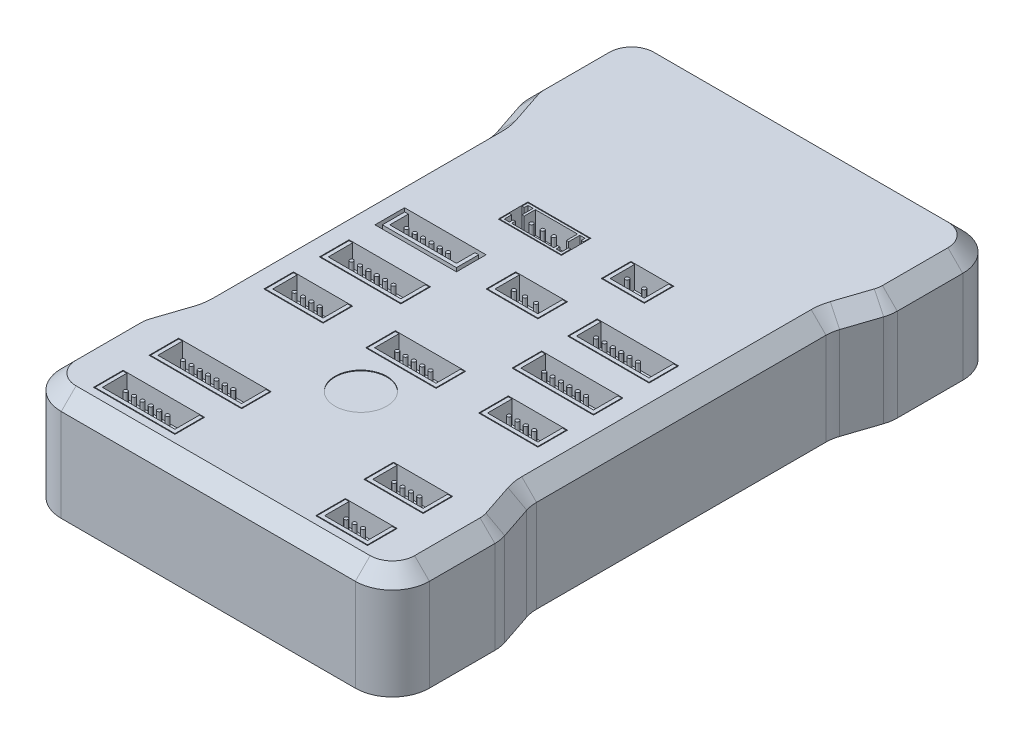
SolidWorks part; units mm, degrees
ref_plane "Front Plane" through (0, 0, 0) normal (0, 0, 1) x (1, 0, 0)
ref_plane "Top Plane" through (0, 0, 0) normal (0, 1, 0) x (1, 0, 0)
ref_plane "Right Plane" through (0, 0, 0) normal (1, 0, 0) x (0, 0, -1)
sketch "Sketch1" plane through (0, 0, 0) normal (0, 1, 0) x (1, 0, 0)
  line L6 (-19.85, 41) -> (19.85, 41)
  line L7 (24.85, 36) -> (24.85, 27.1614)
  line L8 (24.5934, 25.5802) -> (23.1066, 21.1198)
  line L9 (22.85, 19.5386) -> (22.85, -19.5386)
  line L12 (-22.85, 19.5386) -> (-22.85, -19.5386)
  line L13 (-24.5934, 25.5802) -> (-23.1066, 21.1198)
  line L14 (-24.85, 36) -> (-24.85, 27.1614)
  line L15 (-24.85, -36) -> (-24.85, -27.1614)
  line L16 (-24.5934, -25.5802) -> (-23.1066, -21.1198)
  line L17 (24.5934, -25.5802) -> (23.1066, -21.1198)
  line L18 (24.85, -36) -> (24.85, -27.1614)
  line L19 (-19.85, -41) -> (19.85, -41)
  arc A0 (19.85, 41) -> (24.85, 36) centre (19.85, 36) cw
  arc A1 (23.1066, 21.1198) -> (22.85, 19.5386) centre (27.85, 19.5386) ccw
  arc A2 (24.85, 27.1614) -> (24.5934, 25.5802) centre (19.85, 27.1614) cw
  arc A3 (-23.1066, 21.1198) -> (-22.85, 19.5386) centre (-27.85, 19.5386) cw
  arc A4 (-24.85, 27.1614) -> (-24.5934, 25.5802) centre (-19.85, 27.1614) ccw
  arc A5 (-19.85, 41) -> (-24.85, 36) centre (-19.85, 36) ccw
  arc A6 (-19.85, -41) -> (-24.85, -36) centre (-19.85, -36) cw
  arc A7 (-24.85, -27.1614) -> (-24.5934, -25.5802) centre (-19.85, -27.1614) cw
  arc A8 (-23.1066, -21.1198) -> (-22.85, -19.5386) centre (-27.85, -19.5386) ccw
  arc A9 (24.85, -27.1614) -> (24.5934, -25.5802) centre (19.85, -27.1614) ccw
  arc A10 (23.1066, -21.1198) -> (22.85, -19.5386) centre (27.85, -19.5386) cw
  arc A11 (19.85, -41) -> (24.85, -36) centre (19.85, -36) ccw
  point P8 (24.85, 41)
  point P12 (22.85, 20.35)
  point P15 (24.85, 26.35)
  point P44 (24.85, -26.35)
  point P45 (22.85, -20.35)
  point P46 (24.85, -41)
  point P48 (0, 0)
  dimension "D6" = 5
  dimension "D7" = 5
  dimension "D1" = 49.7
  dimension "D2" = 39.0772
  dimension "D3" = 82
  dimension "D4" = 2
  dimension "D5" = 6
  dimension "D8" = 41
extrude "Boss-Extrude1" add sketch "Sketch1" along normal blind 16
chamfer "Chamfer2" distance 2 angle 45 24 edges at (22.9146, 16, 20.3395) (22.85, 16, 0) (23.85, 16, 23.35) (22.9146, 16, -20.3395) (24.7854, 16, 26.3605) (23.85, 16, -23.35) (24.85, 16, 31.5807) (24.7854, 16, -26.3605) (23.3855, 16, 39.5355) (24.85, 16, -31.5807) (0, 16, 41) (23.3855, 16, -39.5355) (-23.3855, 16, 39.5355) (0, 16, -41) (-24.85, 16, 31.5807) (-23.3855, 16, -39.5355) (-24.7854, 16, 26.3605) (-24.85, 16, -31.5807) (-23.85, 16, 23.35) (-24.7854, 16, -26.3605) (-22.9146, 16, 20.3395) (-23.85, 16, -23.35) (-22.85, 16, 0) (-22.9146, 16, -20.3395)
chamfer "Chamfer3" distance 3.5 distance2 1.5 24 edges at (-22.85, 0, 0) (-22.9146, 0, 20.3395) (-22.9146, 0, -20.3395) (-23.85, 0, 23.35) (-23.85, 0, -23.35) (-24.7854, 0, 26.3605) (-24.7854, 0, -26.3605) (-24.85, 0, 31.5807) (-24.85, 0, -31.5807) (-23.3855, 0, 39.5355) (-23.3855, 0, -39.5355) (0, 0, 41) (0, 0, -41) (23.3855, 0, 39.5355) (23.3855, 0, -39.5355) (24.85, 0, 31.5807) (24.85, 0, -31.5807) (24.7854, 0, 26.3605) (24.7854, 0, -26.3605) (23.85, 0, 23.35) (23.85, 0, -23.35) (22.9146, 0, 20.3395) (22.9146, 0, -20.3395) (22.85, 0, 0) first distance on face at (0, 0, 0)
sketch "Sketch4" plane through (0, 0, 0) normal (0, -1, 0) x (1, 0, 0)
  line L0 (0, 0) -> (0, 37.5) construction
  line L1 (-18.35, 36.5) -> (-12.35, 36.5)
  line L2 (-20.35, 34.5) -> (-20.35, 28.5)
  line L3 (-18.35, 26.5) -> (-12.35, 26.5)
  line L4 (-10.35, 34.5) -> (-10.35, 28.5)
  line L5 (19.85, 37.5) -> (-19.85, 37.5) construction
  line L6 (0, 0) -> (-19.35, 0) construction
  line L7 (-19.35, 19.5386) -> (-19.35, -19.5386) construction
  line L8 (-21.35, 36) -> (-21.35, 27.1614) construction
  line L9 (18.35, 26.5) -> (12.35, 26.5)
  line L10 (10.35, 34.5) -> (10.35, 28.5)
  line L11 (18.35, 36.5) -> (12.35, 36.5)
  line L12 (20.35, 34.5) -> (20.35, 28.5)
  line L13 (20.35, -34.5) -> (20.35, -28.5)
  line L14 (18.35, -36.5) -> (12.35, -36.5)
  line L15 (10.35, -34.5) -> (10.35, -28.5)
  line L16 (18.35, -26.5) -> (12.35, -26.5)
  line L17 (-18.35, -26.5) -> (-12.35, -26.5)
  line L18 (-10.35, -34.5) -> (-10.35, -28.5)
  line L19 (-18.35, -36.5) -> (-12.35, -36.5)
  line L20 (-20.35, -34.5) -> (-20.35, -28.5)
  line L22 (-10.75, 17.75) -> (10.75, 17.75)
  line L23 (-12.75, 15.75) -> (-12.75, -15.75)
  line L24 (-10.75, -17.75) -> (10.75, -17.75)
  line L25 (12.75, 15.75) -> (12.75, -15.75)
  arc A0 (-12.35, 26.5) -> (-10.35, 28.5) centre (-12.35, 28.5) ccw
  arc A1 (-20.35, 28.5) -> (-18.35, 26.5) centre (-18.35, 28.5) ccw
  arc A2 (-18.35, 36.5) -> (-20.35, 34.5) centre (-18.35, 34.5) ccw
  arc A3 (-12.35, 36.5) -> (-10.35, 34.5) centre (-12.35, 34.5) cw
  arc A4 (12.35, 26.5) -> (10.35, 28.5) centre (12.35, 28.5) cw
  arc A5 (12.35, 36.5) -> (10.35, 34.5) centre (12.35, 34.5) ccw
  arc A6 (20.35, 28.5) -> (18.35, 26.5) centre (18.35, 28.5) cw
  arc A7 (18.35, 36.5) -> (20.35, 34.5) centre (18.35, 34.5) cw
  arc A8 (20.35, -28.5) -> (18.35, -26.5) centre (18.35, -28.5) ccw
  arc A9 (18.35, -36.5) -> (20.35, -34.5) centre (18.35, -34.5) ccw
  arc A10 (12.35, -36.5) -> (10.35, -34.5) centre (12.35, -34.5) cw
  arc A11 (12.35, -26.5) -> (10.35, -28.5) centre (12.35, -28.5) ccw
  arc A12 (-12.35, -26.5) -> (-10.35, -28.5) centre (-12.35, -28.5) cw
  arc A13 (-12.35, -36.5) -> (-10.35, -34.5) centre (-12.35, -34.5) ccw
  arc A14 (-20.35, -28.5) -> (-18.35, -26.5) centre (-18.35, -28.5) cw
  arc A15 (-18.35, -36.5) -> (-20.35, -34.5) centre (-18.35, -34.5) cw
  arc A16 (-12.75, -15.75) -> (-10.75, -17.75) centre (-10.75, -15.75) ccw
  arc A17 (10.75, -17.75) -> (12.75, -15.75) centre (10.75, -15.75) ccw
  arc A18 (10.75, 17.75) -> (12.75, 15.75) centre (10.75, 15.75) cw
  arc A19 (-10.75, 17.75) -> (-12.75, 15.75) centre (-10.75, 15.75) ccw
  point P16 (-10.35, 26.5)
  point P19 (-20.35, 26.5)
  point P24 (-10.35, 36.5)
  point P65 (0, -17.75)
  point P66 (-12.75, 0)
  point P69 (-12.75, -17.75)
  point P72 (12.75, -17.75)
  point P75 (12.75, 17.75)
  dimension "D5" = 2
  dimension "D8" = 2
  dimension "D1" = 10
  dimension "D2" = 10
  dimension "D3" = 1
  dimension "D4" = 1
  dimension "D6" = 35.5
  dimension "D7" = 25.5
extrude "Cut-Extrude2" cut sketch "Sketch4" against normal blind 0.5
sketch "Sketch5" plane through (0, 16, 0) normal (0, 1, 0) x (1, 0, 0)
  line L0 (-20.85, 19.5386) -> (-20.85, -19.5386) construction
  line L1 (-10.85, 13) -> (-2.35, 13)
  line L2 (-10.85, 13) -> (-10.85, 9)
  line L3 (-10.85, 9) -> (-2.35, 9)
  line L4 (-2.35, 13) -> (-2.35, 9)
  line L5 (3.05, 13) -> (8.85, 13)
  line L6 (3.05, 13) -> (3.05, 9)
  line L7 (3.05, 9) -> (8.85, 9)
  line L8 (8.85, 13) -> (8.85, 9)
  line L9 (20.85, -19.5386) -> (20.85, 19.5386) construction
  line L10 (19.85, 39) -> (-19.85, 39) construction
  line L11 (-18.5, -3.5) -> (-7.5, -3.5)
  line L12 (-18.5, 4) -> (-7.5, 4)
  line L13 (-18.5, 4) -> (-18.5, 0)
  line L14 (-18.5, 0) -> (-7.5, 0)
  line L15 (-7.5, 4) -> (-7.5, 0)
  line L16 (-3.5, 4) -> (3.5, 4)
  line L17 (-3.5, 4) -> (-3.5, 0)
  line L18 (-3.5, 0) -> (3.5, 0)
  line L19 (3.5, 4) -> (3.5, 0)
  line L20 (7.5, 4) -> (18.5, 4)
  line L21 (7.5, 4) -> (7.5, 0)
  line L22 (7.5, 0) -> (18.5, 0)
  line L23 (18.5, 4) -> (18.5, 0)
  line L24 (-18.5, -3.5) -> (-18.5, -7.5)
  line L25 (-18.5, -7.5) -> (-7.5, -7.5)
  line L26 (-7.5, -3.5) -> (-7.5, -7.5)
  line L27 (7.5, -3.5) -> (18.5, -3.5)
  line L28 (7.5, -3.5) -> (7.5, -7.5)
  line L29 (7.5, -7.5) -> (18.5, -7.5)
  line L30 (18.5, -3.5) -> (18.5, -7.5)
  line L31 (-19.85, -39) -> (19.85, -39) construction
  line L32 (-18.5, -11) -> (-10.5, -11)
  line L33 (-18.5, -11) -> (-18.5, -15)
  line L34 (-18.5, -15) -> (-10.5, -15)
  line L35 (-10.5, -11) -> (-10.5, -15)
  line L36 (-4.75, -11) -> (4.75, -11)
  line L37 (-4.75, -11) -> (-4.75, -15)
  line L38 (-4.75, -15) -> (4.75, -15)
  line L39 (4.75, -11) -> (4.75, -15)
  line L40 (10.5, -11) -> (18.5, -11)
  line L41 (10.5, -11) -> (10.5, -15)
  line L42 (10.5, -15) -> (18.5, -15)
  line L43 (18.5, -11) -> (18.5, -15)
  line L44 (-18.5, -34) -> (-7.5, -34)
  line L45 (-18.5, -34) -> (-18.5, -38)
  line L46 (-18.5, -38) -> (-7.5, -38)
  line L47 (-7.5, -34) -> (-7.5, -38)
  line L49 (-18.5, -26.5) -> (-6, -26.5)
  line L50 (-18.5, -26.5) -> (-18.5, -30.5)
  line L51 (-18.5, -30.5) -> (-6, -30.5)
  line L52 (-6, -26.5) -> (-6, -30.5)
  line L53 (18.5, -26.5) -> (10.5, -26.5)
  line L54 (18.5, -26.5) -> (18.5, -30.5)
  line L55 (18.5, -30.5) -> (10.5, -30.5)
  line L56 (10.5, -26.5) -> (10.5, -30.5)
  line L57 (18.5, -34) -> (11.5, -34)
  line L58 (18.5, -34) -> (18.5, -38)
  line L59 (18.5, -38) -> (11.5, -38)
  line L60 (11.5, -34) -> (11.5, -38)
  point P12 (3.05, 11)
  point P13 (-2.35, 11)
  point P49 (0, 4)
  point P51 (0, -11)
  dimension "D1" = 8.5
  dimension "D2" = 4
  dimension "D3" = 4
  dimension "D4" = 5.8
  dimension "D5" = 10
  dimension "D6" = 12
  dimension "D7" = 26
  dimension "D8" = 11
  dimension "D9" = 4
  dimension "D10" = 4
  dimension "D11" = 4
  dimension "D12" = 7
  dimension "D13" = 4
  dimension "D14" = 4
  dimension "D15" = 11
  dimension "D16" = 5
  dimension "D17" = 8
  dimension "D18" = 11
  dimension "D19" = 4
  dimension "D20" = 4
  dimension "D21" = 11
  dimension "D22" = 3.5
  dimension "D23" = 3.5
  dimension "D24" = 8
  dimension "D25" = 4
  dimension "D26" = 3.5
  dimension "D27" = 9.5
  dimension "D28" = 4
  dimension "D29" = 4
  dimension "D30" = 11
  dimension "D31" = 4
  dimension "D32" = 1
  dimension "D33" = 12.5
  dimension "D34" = 4
  dimension "D35" = 3.5
  dimension "D36" = 8
  dimension "D37" = 4
  dimension "D38" = 7
  dimension "D39" = 4
  dimension "D40" = 1
  dimension "D41" = 3.5
extrude "Cut-Extrude3" cut sketch "Sketch5" against normal blind 4
sketch "Sketch6" plane through (0, 12, 0) normal (0, 1, 0) x (1, 0, 0)
  line L0 (-10.85, 11) -> (-3.85, 11) construction
  line L1 (-10.85, 13) -> (-10.85, 9) construction
  line L2 (-2.35, 9) -> (-2.35, 13) construction
  line L25 (-9.85, 11) -> (-9.35, 11)
  line L27 (-6.6, 11) -> (-6.6, 9.5) construction
  line L46 (-9.45, 12.6) -> (-3.75, 12.6)
  line L47 (-3.75, 11.1) -> (-3.75, 12.6)
  line L48 (-3.45, 11.1) -> (-3.75, 11.1)
  line L49 (-3.45, 12.6) -> (-3.45, 11.1)
  line L50 (-2.75, 12.6) -> (-3.45, 12.6)
  line L51 (-2.75, 12.1) -> (-2.75, 12.6)
  line L52 (-2.45, 12.1) -> (-2.75, 12.1)
  line L53 (-2.45, 12.9) -> (-2.45, 12.1)
  line L54 (-10.75, 12.9) -> (-2.45, 12.9)
  line L55 (-10.75, 12.1) -> (-10.75, 12.9)
  line L56 (-10.75, 12.1) -> (-10.45, 12.1)
  line L57 (-10.45, 12.1) -> (-10.45, 12.6)
  line L58 (-10.45, 12.6) -> (-9.75, 12.6)
  line L59 (-9.75, 12.6) -> (-9.75, 11.1)
  line L60 (-9.75, 11.1) -> (-9.45, 11.1)
  line L61 (-9.45, 11.1) -> (-9.45, 12.6)
  line L62 (-2.75, 9.4) -> (-2.75, 10.4)
  line L63 (-2.75, 10.4) -> (-2.45, 10.4)
  line L64 (-2.45, 10.4) -> (-2.45, 9.1)
  line L65 (-10.75, 9.1) -> (-2.45, 9.1)
  line L66 (-10.75, 10.4) -> (-10.75, 9.1)
  line L67 (-10.45, 10.4) -> (-10.75, 10.4)
  line L68 (-10.45, 9.4) -> (-10.45, 10.4)
  line L69 (-9.75, 9.4) -> (-10.45, 9.4)
  line L70 (-9.75, 9.9) -> (-9.75, 9.4)
  line L71 (-9.45, 9.9) -> (-9.75, 9.9)
  line L72 (-9.45, 9.4) -> (-9.45, 9.9)
  line L73 (-3.75, 9.4) -> (-9.45, 9.4)
  line L74 (-3.75, 9.4) -> (-3.75, 9.9)
  line L75 (-3.75, 9.9) -> (-3.45, 9.9)
  line L76 (-3.45, 9.9) -> (-3.45, 9.4)
  line L77 (-3.45, 9.4) -> (-2.75, 9.4)
  line L78 (-10.85, 12) -> (-10.85, 13) construction
  line L79 (-10.85, 13) -> (-2.35, 13) construction
  line L80 (-10.85, 12) -> (-10.35, 12) construction
  line L81 (-10.35, 12) -> (-10.35, 12.5) construction
  line L82 (-10.35, 12.5) -> (-9.85, 12.5) construction
  line L83 (-9.85, 12.5) -> (-9.85, 11) construction
  line L84 (-2.35, 13) -> (-2.35, 12) construction
  line L85 (-2.35, 12) -> (-2.85, 12) construction
  line L86 (-2.85, 12) -> (-2.85, 12.5) construction
  line L87 (-2.85, 12.5) -> (-3.35, 12.5) construction
  line L88 (-3.35, 12.5) -> (-3.35, 11) construction
  line L89 (-3.35, 11) -> (-2.35, 11) construction
  line L90 (-3.35, 11) -> (-3.85, 11) construction
  line L91 (-3.85, 11) -> (-3.85, 12.5) construction
  line L92 (-9.35, 12.5) -> (-3.85, 12.5) construction
  line L93 (-9.35, 11) -> (-9.35, 12.5) construction
  dimension "D2" = 0.5
  dimension "D8" = 0.1
extrude "Boss-Extrude2" add sketch "Sketch6" along normal up to surface (4 mm away) contours L60 L61 L46 L47 L48 L49 L50 L51 L52 L53 L54 L55 L56 L57 L58 L59 | L77 L76 L75 L74 L73 L72 L71 L70 L69 L68 L67 L66 L65 L64 L63 L62 region at (-9.5349, 12, -11.85) region at (-2.666, 12, -9.9) up to face at (13, 16, -2)
sketch "Sketch7" plane through (0, 12, 0) normal (0, 1, 0) x (1, 0, 0)
  line L0 (-10.75, 9.1) -> (-2.45, 9.1) construction
  line L1 (-10.75, 12.9) -> (-2.45, 12.9) construction
  line L2 (-10.75, 9.1) -> (-2.45, 9.1)
  line L3 (-10.75, 12.9) -> (-2.45, 12.9)
  line L4 (-10.75, 12.9) -> (-10.75, 9.1)
  line L5 (-2.45, 12.9) -> (-2.45, 9.1)
extrude "Boss-Extrude3" add sketch "Sketch7" along normal blind 1
sketch "Sketch8" plane through (0, 13, 0) normal (0, 1, 0) x (1, 0, 0)
  line L6 (-10.75, 11) -> (-2.45, 11) construction
  circle A0 centre (-6.6, 10.75) radius 0.25
  circle A1 centre (-5.1, 10.75) radius 0.25
  circle A2 centre (-8.1, 10.75) radius 0.25
  point P9 (-6.6, 11)
  dimension "D1" = 0.5
  dimension "D2" = 0.25
  dimension "D3" = 1.5
  dimension "D4" = 1.5
extrude "Boss-Extrude4" add sketch "Sketch8" along normal up to surface (3 mm away) up to face at (13, 16, -2)
sketch "Sketch9" plane through (0, 12, 0) normal (0, 1, 0) x (1, 0, 0)
  line L0 (8.75, 12.9) -> (8.25, 12.9)
  line L1 (3.15, 12.9) -> (3.15, 9.1)
  line L2 (3.15, 9.1) -> (8.75, 9.1)
  line L3 (8.75, 9.1) -> (8.75, 12.9)
  line L4 (3.65, 12.9) -> (3.65, 9.6)
  line L5 (3.65, 9.6) -> (8.25, 9.6)
  line L6 (8.25, 9.6) -> (8.25, 12.9)
  line L7 (3.65, 12.9) -> (3.15, 12.9)
  line L8 (3.05, 13) -> (3.05, 9) construction
  line L9 (3.05, 9) -> (8.85, 9) construction
  line L10 (8.85, 9) -> (8.85, 13) construction
  line L11 (8.85, 13) -> (3.05, 13) construction
  dimension "D1" = 0.5
  dimension "D2" = 0.1
  dimension "D3" = 0.1
  dimension "D4" = 0.5
  dimension "D5" = 0.1
  dimension "D6" = 0.5
  dimension "D7" = 0.1
extrude "Boss-Extrude5" add sketch "Sketch9" along normal up to surface (4 mm away) up to face at (13, 16, -2)
sketch "Sketch10" plane through (0, 12, 0) normal (0, 1, 0) x (1, 0, 0)
  line L0 (8.75, 12.9) -> (8.75, 9.1) construction
  line L1 (3.15, 9.1) -> (8.75, 9.1) construction
  line L2 (3.15, 9.1) -> (3.15, 12.9) construction
  line L3 (3.15, 12.9) -> (3.65, 12.9) construction
  line L4 (8.75, 12.9) -> (8.75, 9.1)
  line L5 (3.15, 9.1) -> (8.75, 9.1)
  line L6 (3.15, 9.1) -> (3.15, 12.9)
  line L7 (3.15, 12.9) -> (3.65, 12.9)
  line L8 (3.65, 12.9) -> (8.75, 12.9)
extrude "Boss-Extrude6" add sketch "Sketch10" along normal blind 1
sketch "Sketch11" plane through (0, 13, 0) normal (0, 1, 0) x (1, 0, 0)
  line L0 (3.15, 11) -> (8.75, 11) construction
  line L1 (3.15, 12.9) -> (3.15, 9.1) construction
  line L2 (8.75, 9.1) -> (8.75, 12.9) construction
  circle A0 centre (4.8, 10.75) radius 0.25
  circle A1 centre (7.1, 10.75) radius 0.25
  point P10 (5.95, 11)
  dimension "D1" = 0.5
  dimension "D2" = 1.15
  dimension "D3" = 1.15
extrude "Boss-Extrude7" add sketch "Sketch11" along normal up to surface (3 mm away) up to face at (13, 16, -2)
sketch "Sketch12" plane through (0, 12, 0) normal (0, 1, 0) x (1, 0, 0)
  line L0 (-8, 3.5) -> (-18, 3.5)
  line L1 (-18, 3.5) -> (-18, 0.5)
  line L2 (-18, 0.5) -> (-8, 0.5)
  line L3 (-8, 0.5) -> (-8, 3.5)
extrude "Boss-Extrude8" add sketch "Sketch12" along normal blind 1
sketch "Sketch13" plane through (0, 13, 0) normal (0, 1, 0) x (1, 0, 0)
  line L0 (-18, 3.5) -> (-18, 0.5)
  line L1 (-18, 0.5) -> (-8, 0.5)
  line L2 (-8, 0.5) -> (-8, 3.5)
  line L3 (-8, 3.5) -> (-8.5, 3.5)
  line L4 (-8, 3.5) -> (-18, 3.5) construction
  line L5 (-8.5, 3.5) -> (-8.5, 1)
  line L6 (-8.5, 1) -> (-17.5, 1)
  line L7 (-17.5, 1) -> (-17.5, 3.5)
  line L8 (-17.5, 3.5) -> (-18, 3.5)
  dimension "D1" = 0.5
  dimension "D2" = 0.5
  dimension "D3" = 0.5
extrude "Boss-Extrude9" add sketch "Sketch13" along normal up to surface (3 mm away) up to face at (13, 16, -2)
sketch "Sketch14" plane through (0, 13, 0) normal (0, 1, 0) x (1, 0, 0)
  line L0 (-17.5, 2) -> (-8.5, 2) construction
  line L1 (-17.5, 1) -> (-17.5, 3.5) construction
  line L3 (-17.5, 3.5) -> (-17.5, 1) construction
  line L4 (-8.5, 1) -> (-8.5, 3.5) construction
  circle A0 centre (-16, 1.75) radius 0.25
  circle A1 centre (-14.875, 1.75) radius 0.25
  circle A2 centre (-13.75, 1.75) radius 0.25
  circle A3 centre (-12.625, 1.75) radius 0.25
  circle A5 centre (-11.5, 1.75) radius 0.25
  circle A6 centre (-10.375, 1.75) radius 0.25
  dimension "D1" = 0.5
  dimension "D2" = 1.5
  dimension "D3" = 1.125
  dimension "D4" = 1.125
  dimension "D5" = 1.125
  dimension "D6" = 1.125
  dimension "D7" = 1.125
extrude "Boss-Extrude10" add sketch "Sketch14" along normal up to surface (3 mm away) up to face at (13, 16, -2)
sketch "Sketch15" plane through (0, 12, 0) normal (0, 1, 0) x (1, 0, 0)
  line L0 (3.4, 3.9) -> (-3.4, 3.9)
  line L1 (-3.4, 3.9) -> (-3.4, 0.1)
  line L2 (-3.4, 0.1) -> (3.4, 0.1)
  line L3 (3.4, 0.1) -> (3.4, 3.9)
extrude "Boss-Extrude11" add sketch "Sketch15" along normal blind 1
sketch "Sketch16" plane through (0, 13, 0) normal (0, 1, 0) x (1, 0, 0)
  line L0 (-3.4, 0.1) -> (-3.4, 3.9)
  line L1 (-3.4, 3.9) -> (-2.9, 3.9)
  line L2 (3.4, 3.9) -> (-3.4, 3.9) construction
  line L3 (-2.9, 3.9) -> (-2.9, 0.6)
  line L4 (-2.9, 0.6) -> (2.9, 0.6)
  line L5 (2.9, 0.6) -> (2.9, 3.9)
  line L6 (2.9, 3.9) -> (3.4, 3.9)
  line L7 (3.4, 0.1) -> (3.4, 3.9) construction
  line L8 (3.4, 3.9) -> (3.4, 0.1)
  line L9 (3.4, 0.1) -> (-3.4, 0.1)
  point P15 (3.4, 2)
  dimension "D1" = 0.5
  dimension "D2" = 0.5
  dimension "D3" = 0.5
extrude "Boss-Extrude12" add sketch "Sketch16" along normal up to surface (3 mm away) up to face at (13, 16, -2)
sketch "Sketch17" plane through (0, 13, 0) normal (0, 1, 0) x (1, 0, 0)
  line L0 (-2.9, 2) -> (2.9, 2) construction
  line L1 (-2.9, 3.9) -> (-2.9, 0.6) construction
  line L2 (2.9, 3.9) -> (2.9, 0.6) construction
  circle A0 centre (0, 1.75) radius 0.25
  circle A1 centre (-1.5, 1.75) radius 0.25
  circle A2 centre (1.5, 1.75) radius 0.25
  point P14 (0, 1.5109)
  dimension "D1" = 0.5
  dimension "D2" = 0.5
  dimension "D3" = 1.5
  dimension "D4" = 1.5
extrude "Boss-Extrude13" add sketch "Sketch17" along normal up to surface (3 mm away) up to face at (13, 16, -2)
sketch "Sketch18" plane through (0, 12, 0) normal (0, 1, 0) x (1, 0, 0)
  line L0 (18.4, 3.9) -> (7.6, 3.9)
  line L1 (7.6, 3.9) -> (7.6, 0.1)
  line L2 (7.6, 0.1) -> (18.4, 0.1)
  line L3 (18.4, 0.1) -> (18.4, 3.9)
extrude "Boss-Extrude14" add sketch "Sketch18" along normal blind 1
sketch "Sketch19" plane through (0, 13, 0) normal (0, 1, 0) x (1, 0, 0)
  line L0 (7.6, 0.1) -> (7.6, 3.9)
  line L1 (7.6, 3.9) -> (8.1, 3.9)
  line L2 (18.4, 3.9) -> (7.6, 3.9) construction
  line L3 (8.1, 3.9) -> (8.1, 0.6)
  line L4 (8.1, 0.6) -> (17.9, 0.6)
  line L5 (17.9, 0.6) -> (17.9, 3.9)
  line L6 (17.9, 3.9) -> (18.4, 3.9)
  line L7 (18.4, 3.9) -> (7.6, 3.9) construction
  line L8 (18.4, 3.9) -> (18.4, 0.1)
  line L9 (18.4, 0.1) -> (7.6, 0.1)
  dimension "D1" = 0.5
  dimension "D2" = 0.5
  dimension "D3" = 0.5
extrude "Boss-Extrude15" add sketch "Sketch19" along normal up to surface (3 mm away) up to face at (13, 16, -2)
sketch "Sketch20" plane through (0, 13, 0) normal (0, 1, 0) x (1, 0, 0)
  line L0 (8.1, 1.997) -> (17.9, 1.997) construction
  line L1 (8.1, 3.9) -> (8.1, 0.6) construction
  line L2 (17.9, 3.9) -> (17.9, 0.6) construction
  line L3 (8.1, 0.6) -> (8.1, 3.9) construction
  circle A0 centre (14.1223, 1.747) radius 0.25
  circle A1 centre (15.2523, 1.747) radius 0.25
  circle A2 centre (11.8623, 1.75) radius 0.247
  circle A3 centre (10.7323, 1.747) radius 0.25
  circle A4 centre (12.9923, 1.75) radius 0.247
  circle A5 centre (9.6, 1.747) radius 0.25
  dimension "D1" = 0.5
  dimension "D2" = 0.5
  dimension "D3" = 1.1323
  dimension "D4" = 1.13
  dimension "D5" = 1.13
  dimension "D6" = 1.13
  dimension "D7" = 1.13
  dimension "D8" = 1.5
extrude "Boss-Extrude16" add sketch "Sketch20" along normal up to surface (3 mm away) up to face at (13, 16, -2)
sketch "Sketch22" plane through (0, 12, 0) normal (0, 1, 0) x (1, 0, 0)
  line L0 (-7.6, -3.6) -> (-18.4, -3.6)
  line L1 (-18.4, -3.6) -> (-18.4, -7.4)
  line L2 (-18.4, -7.4) -> (-7.6, -7.4)
  line L3 (-7.6, -7.4) -> (-7.6, -3.6)
extrude "Boss-Extrude17" add sketch "Sketch22" along normal blind 1
sketch "Sketch23" plane through (0, 13, 0) normal (0, 1, 0) x (1, 0, 0)
  line L0 (-18.4, -7.4) -> (-18.4, -3.6)
  line L1 (-18.4, -3.6) -> (-18.4, -7.4) construction
  line L2 (-18.4, -3.6) -> (-18.4, -7.4) construction
  line L3 (-18.4, -3.6) -> (-17.9, -3.6)
  line L4 (-7.6, -3.6) -> (-18.4, -3.6) construction
  line L5 (-17.9, -3.6) -> (-17.9, -6.9)
  line L6 (-17.9, -6.9) -> (-8.1, -6.9)
  line L7 (-8.1, -6.9) -> (-8.1, -3.6)
  line L8 (-8.1, -3.6) -> (-7.6, -3.6)
  line L9 (-7.6, -3.6) -> (-18.4, -3.6) construction
  line L10 (-7.6, -3.6) -> (-7.6, -7.4)
  line L11 (-7.6, -7.4) -> (-18.4, -7.4)
  dimension "D1" = 0.5
  dimension "D2" = 0.5
  dimension "D3" = 0.5
extrude "Boss-Extrude18" add sketch "Sketch23" along normal up to surface (3 mm away) up to face at (13, 16, -2)
sketch "Sketch24" plane through (0, 13, 0) normal (0, 1, 0) x (1, 0, 0)
  line L0 (-17.9, -5.5) -> (-8.1, -5.5) construction
  line L1 (-17.9, -3.6) -> (-17.9, -6.9) construction
  line L2 (-8.1, -3.6) -> (-8.1, -6.9) construction
  line L3 (-17.9, -6.9) -> (-17.9, -3.6) construction
  circle A0 centre (-15.9, -5.75) radius 0.25
  circle A1 centre (-14.77, -5.75) radius 0.25
  circle A2 centre (-13.64, -5.75) radius 0.25
  circle A3 centre (-12.51, -5.75) radius 0.25
  circle A4 centre (-11.38, -5.75) radius 0.25
  circle A5 centre (-10.25, -5.75) radius 0.25
  dimension "D1" = 0.5
  dimension "D2" = 2
  dimension "D3" = 6
extrude "Boss-Extrude19" add sketch "Sketch24" along normal up to surface (3 mm away) up to face at (13, 16, -2)
sketch "Sketch25" plane through (0, 12, 0) normal (0, 1, 0) x (1, 0, 0)
  line L0 (18.4, -3.6) -> (7.6, -3.6)
  line L1 (7.6, -3.6) -> (7.6, -7.4)
  line L2 (7.6, -7.4) -> (18.4, -7.4)
  line L3 (18.4, -7.4) -> (18.4, -3.6)
extrude "Boss-Extrude20" add sketch "Sketch25" along normal blind 1
sketch "Sketch26" plane through (0, 13, 0) normal (0, 1, 0) x (1, 0, 0)
  line L0 (7.6, -3.6) -> (7.6, -7.4)
  line L1 (7.6, -7.4) -> (18.4, -7.4)
  line L2 (18.4, -7.4) -> (18.4, -3.6)
  line L3 (18.4, -3.6) -> (17.9, -3.6)
  line L4 (18.4, -3.6) -> (7.6, -3.6) construction
  line L5 (17.9, -3.6) -> (17.9, -6.9)
  line L6 (17.9, -6.9) -> (8.1, -6.9)
  line L7 (8.1, -6.9) -> (8.1, -3.6)
  line L8 (8.1, -3.6) -> (7.6, -3.6)
  dimension "D1" = 0.5
  dimension "D2" = 0.5
  dimension "D3" = 0.5
extrude "Boss-Extrude21" add sketch "Sketch26" along normal up to surface (3 mm away) up to face at (13, 16, -2)
sketch "Sketch27" plane through (0, 13, 0) normal (0, 1, 0) x (1, 0, 0)
  line L0 (8.1, -5.5) -> (17.9, -5.5) construction
  line L1 (8.1, -3.6) -> (8.1, -6.9) construction
  line L2 (17.9, -3.6) -> (17.9, -6.9) construction
  circle A0 centre (10.1, -5.75) radius 0.25
  circle A1 centre (11.23, -5.75) radius 0.25
  circle A2 centre (12.36, -5.75) radius 0.25
  circle A3 centre (13.49, -5.75) radius 0.25
  circle A4 centre (14.62, -5.75) radius 0.25
  circle A5 centre (15.75, -5.75) radius 0.25
  dimension "D1" = 0.5
  dimension "D2" = 2
  dimension "D3" = 6
extrude "Boss-Extrude22" add sketch "Sketch27" along normal up to surface (3 mm away) up to face at (13, 16, -2)
sketch "Sketch28" plane through (0, 12, 0) normal (0, 1, 0) x (1, 0, 0)
  line L0 (-10.6, -11.1) -> (-18.4, -11.1)
  line L1 (-18.4, -11.1) -> (-18.4, -14.9)
  line L2 (-18.4, -14.9) -> (-10.6, -14.9)
  line L3 (-10.6, -14.9) -> (-10.6, -11.1)
extrude "Boss-Extrude23" add sketch "Sketch28" along normal blind 1
sketch "Sketch29" plane through (0, 13, 0) normal (0, 1, 0) x (1, 0, 0)
  line L0 (-18.4, -11.1) -> (-18.4, -14.9)
  line L1 (-18.4, -14.9) -> (-10.6, -14.9)
  line L2 (-10.6, -14.9) -> (-10.6, -11.1)
  line L3 (-10.6, -11.1) -> (-11.1, -11.1)
  line L4 (-10.6, -11.1) -> (-18.4, -11.1) construction
  line L5 (-11.1, -11.1) -> (-11.1, -14.4)
  line L6 (-11.1, -14.4) -> (-17.9, -14.4)
  line L7 (-17.9, -14.4) -> (-17.9, -11.1)
  line L8 (-17.9, -11.1) -> (-18.4, -11.1)
  dimension "D1" = 0.5
  dimension "D2" = 0.5
  dimension "D3" = 0.5
extrude "Boss-Extrude24" add sketch "Sketch29" along normal up to surface (3 mm away) up to face at (13, 16, -2)
sketch "Sketch30" plane through (0, 13, 0) normal (0, 1, 0) x (1, 0, 0)
  line L0 (-17.9, -13) -> (-11.1, -13) construction
  line L1 (-17.9, -11.1) -> (-17.9, -14.4) construction
  line L2 (-11.1, -11.1) -> (-11.1, -14.4) construction
  line L3 (-17.9, -14.4) -> (-17.9, -11.1) construction
  circle A0 centre (-16.1, -13.25) radius 0.25
  circle A1 centre (-14.97, -13.25) radius 0.25
  circle A2 centre (-13.84, -13.25) radius 0.25
  circle A3 centre (-12.71, -13.25) radius 0.25
  dimension "D1" = 0.5
  dimension "D2" = 4
  dimension "D3" = 1.8
extrude "Boss-Extrude25" add sketch "Sketch30" along normal up to surface (3 mm away) up to face at (13, 16, -2)
sketch "Sketch31" plane through (0, 12, 0) normal (0, 1, 0) x (1, 0, 0)
  line L0 (4.65, -11.1) -> (-4.65, -11.1)
  line L1 (-4.65, -11.1) -> (-4.65, -14.9)
  line L2 (-4.65, -14.9) -> (4.65, -14.9)
  line L3 (4.65, -14.9) -> (4.65, -11.1)
extrude "Boss-Extrude26" add sketch "Sketch31" along normal blind 1
sketch "Sketch32" plane through (0, 13, 0) normal (0, 1, 0) x (1, 0, 0)
  line L0 (-4.65, -14.9) -> (-4.65, -11.1)
  line L1 (-4.65, -11.1) -> (-4.15, -11.1)
  line L2 (4.65, -11.1) -> (-4.65, -11.1) construction
  line L3 (-4.15, -11.1) -> (-4.15, -14.4)
  line L4 (-4.15, -14.4) -> (4.15, -14.4)
  line L5 (4.15, -14.4) -> (4.15, -11.1)
  line L6 (4.65, -11.1) -> (-4.65, -11.1) construction
  line L7 (4.15, -11.1) -> (4.65, -11.1)
  line L8 (4.65, -11.1) -> (4.65, -14.9)
  line L9 (4.65, -14.9) -> (-4.65, -14.9)
  dimension "D1" = 0.5
  dimension "D2" = 0.5
  dimension "D3" = 0.5
extrude "Boss-Extrude27" add sketch "Sketch32" along normal up to surface (3 mm away) up to face at (13, 16, -2)
sketch "Sketch33" plane through (0, 13, 0) normal (0, 1, 0) x (1, 0, 0)
  line L0 (-4.15, -13) -> (4.15, -13) construction
  line L1 (-4.15, -14.4) -> (-4.15, -11.1) construction
  line L2 (4.15, -14.4) -> (4.15, -11.1) construction
  circle A0 centre (0, -13.25) radius 0.25
  circle A1 centre (1.13, -13.2565) radius 0.25
  circle A2 centre (-1.13, -13.25) radius 0.25
  circle A5 centre (2.26, -13.263) radius 0.25
  circle A7 centre (-2.26, -13.237) radius 0.25
  point P15 (0, -13.4891)
  dimension "D1" = 0.5
  dimension "D2" = 1.13
  dimension "D3" = 1.13
  dimension "D4" = 1.13
  dimension "D5" = 1.13
extrude "Boss-Extrude28" add sketch "Sketch33" along normal up to surface (3 mm away) up to face at (13, 16, -2)
sketch "Sketch34" plane through (0, 12, 0) normal (0, 1, 0) x (1, 0, 0)
  line L0 (18.4, -11.1) -> (10.6, -11.1)
  line L1 (10.6, -11.1) -> (10.6, -14.9)
  line L2 (10.6, -14.9) -> (18.4, -14.9)
  line L3 (18.4, -14.9) -> (18.4, -11.1)
extrude "Boss-Extrude29" add sketch "Sketch34" along normal blind 1
sketch "Sketch35" plane through (0, 13, 0) normal (0, 1, 0) x (1, 0, 0)
  line L0 (10.6, -11.1) -> (10.6, -14.9)
  line L1 (10.6, -14.9) -> (18.4, -14.9)
  line L2 (18.4, -14.9) -> (18.4, -11.1)
  line L3 (18.4, -11.1) -> (17.9, -11.1)
  line L4 (18.4, -11.1) -> (10.6, -11.1) construction
  line L5 (17.9, -11.1) -> (17.9, -14.4)
  line L6 (17.9, -14.4) -> (11.1, -14.4)
  line L7 (11.1, -14.4) -> (11.1, -11.1)
  line L8 (18.4, -11.1) -> (10.6, -11.1) construction
  line L9 (11.1, -11.1) -> (10.6, -11.1)
  dimension "D1" = 0.5
  dimension "D2" = 0.5
  dimension "D3" = 0.5
extrude "Boss-Extrude30" add sketch "Sketch35" along normal up to surface (3 mm away) up to face at (13, 16, -2)
sketch "Sketch36" plane through (0, 13, 0) normal (0, 1, 0) x (1, 0, 0)
  line L0 (11.1, -13) -> (17.9, -13) construction
  line L1 (11.1, -11.1) -> (11.1, -14.4) construction
  line L2 (17.9, -11.1) -> (17.9, -14.4) construction
  line L3 (11.1, -14.4) -> (11.1, -11.1) construction
  circle A0 centre (12.85, -13.25) radius 0.25
  circle A1 centre (13.98, -13.25) radius 0.25
  circle A2 centre (15.11, -13.25) radius 0.25
  circle A3 centre (16.24, -13.25) radius 0.25
  dimension "D1" = 0.5
  dimension "D3" = 1.75
  dimension "D2" = 4
extrude "Boss-Extrude31" add sketch "Sketch36" along normal up to surface (3 mm away) up to face at (13, 16, -2)
sketch "Sketch37" plane through (0, 12, 0) normal (0, 1, 0) x (1, 0, 0)
  line L0 (-6.1, -26.6) -> (-18.4, -26.6)
  line L1 (-18.4, -26.6) -> (-18.4, -30.4)
  line L2 (-18.4, -30.4) -> (-6.1, -30.4)
  line L3 (-6.1, -30.4) -> (-6.1, -26.6)
extrude "Boss-Extrude32" add sketch "Sketch37" along normal blind 1
sketch "Sketch38" plane through (0, 13, 0) normal (0, 1, 0) x (1, 0, 0)
  line L0 (-18.4, -26.6) -> (-18.4, -30.4)
  line L1 (-18.4, -30.4) -> (-6.1, -30.4)
  line L2 (-6.1, -30.4) -> (-6.1, -26.6)
  line L3 (-6.1, -26.6) -> (-6.6, -26.6)
  line L4 (-6.1, -26.6) -> (-18.4, -26.6) construction
  line L5 (-6.6, -26.6) -> (-6.6, -29.9)
  line L6 (-6.6, -29.9) -> (-17.9, -29.9)
  line L7 (-17.9, -29.9) -> (-17.9, -26.6)
  line L8 (-6.1, -26.6) -> (-18.4, -26.6) construction
  line L9 (-17.9, -26.6) -> (-18.4, -26.6)
  dimension "D1" = 0.5
  dimension "D2" = 0.5
  dimension "D3" = 0.5
extrude "Boss-Extrude33" add sketch "Sketch38" along normal up to surface (3 mm away) up to face at (13, 16, -2)
sketch "Sketch39" plane through (0, 13, 0) normal (0, 1, 0) x (1, 0, 0)
  line L0 (-17.9, -28.5238) -> (-6.6, -28.5238) construction
  line L1 (-17.9, -29.9) -> (-17.9, -26.6) construction
  line L2 (-6.6, -29.9) -> (-6.6, -26.6) construction
  circle A0 centre (-12.25, -28.7738) radius 0.25
  circle A1 centre (-11.12, -28.7738) radius 0.25
  circle A2 centre (-14.51, -28.7738) radius 0.25
  circle A3 centre (-13.38, -28.7738) radius 0.25
  circle A4 centre (-9.99, -28.7738) radius 0.25
  circle A5 centre (-8.86, -28.7738) radius 0.25
  circle A6 centre (-15.64, -28.7738) radius 0.25
  point P21 (-12.25, -29.0129)
  point P23 (-12.25, -28.5238)
  dimension "D1" = 0.5
  dimension "D2" = 1.13
  dimension "D3" = 1.13
  dimension "D4" = 1.13
  dimension "D5" = 1.13
  dimension "D6" = 1.13
  dimension "D7" = 1.13
extrude "Boss-Extrude34" add sketch "Sketch39" along normal up to surface (3 mm away) up to face at (13, 16, -2)
sketch "Sketch40" plane through (0, 12, 0) normal (0, 1, 0) x (1, 0, 0)
  line L0 (18.4, -26.6) -> (10.6, -26.6)
  line L1 (10.6, -26.6) -> (10.6, -30.4)
  line L2 (10.6, -30.4) -> (18.4, -30.4)
  line L3 (18.4, -30.4) -> (18.4, -26.6)
extrude "Boss-Extrude35" add sketch "Sketch40" along normal blind 1
sketch "Sketch41" plane through (0, 13, 0) normal (0, 1, 0) x (1, 0, 0)
  line L0 (10.6, -30.4) -> (10.6, -26.6)
  line L1 (10.6, -26.6) -> (11.1, -26.6)
  line L2 (18.4, -26.6) -> (10.6, -26.6) construction
  line L3 (11.1, -26.6) -> (11.1, -29.9)
  line L4 (11.1, -29.9) -> (17.9, -29.9)
  line L5 (17.9, -29.9) -> (17.9, -26.6)
  line L6 (18.4, -26.6) -> (10.6, -26.6) construction
  line L7 (17.9, -26.6) -> (18.4, -26.6)
  line L8 (18.4, -26.6) -> (18.4, -30.4)
  line L9 (18.4, -30.4) -> (10.6, -30.4)
  dimension "D1" = 0.5
  dimension "D2" = 0.5
  dimension "D3" = 0.5
extrude "Boss-Extrude36" add sketch "Sketch41" along normal up to surface (3 mm away) up to face at (13, 16, -2)
sketch "Sketch42" plane through (0, 13, 0) normal (0, 1, 0) x (1, 0, 0)
  line L0 (11.1, -28.5) -> (17.9, -28.5) construction
  line L1 (11.1, -26.6) -> (11.1, -29.9) construction
  line L2 (17.9, -26.6) -> (17.9, -29.9) construction
  line L3 (11.1, -29.9) -> (11.1, -26.6) construction
  circle A0 centre (12.85, -28.75) radius 0.25
  circle A1 centre (13.98, -28.75) radius 0.25
  circle A2 centre (15.11, -28.75) radius 0.25
  circle A3 centre (16.24, -28.75) radius 0.25
  dimension "D1" = 0.5
  dimension "D3" = 1.75
  dimension "D2" = 4
extrude "Boss-Extrude37" add sketch "Sketch42" along normal up to surface (3 mm away) up to face at (13, 16, -2)
sketch "Sketch43" plane through (0, 12, 0) normal (0, 1, 0) x (1, 0, 0)
  line L0 (-7.6, -34.1) -> (-18.4, -34.1)
  line L1 (-18.4, -34.1) -> (-18.4, -37.9)
  line L2 (-18.4, -37.9) -> (-7.6, -37.9)
  line L3 (-7.6, -37.9) -> (-7.6, -34.1)
extrude "Boss-Extrude38" add sketch "Sketch43" along normal blind 1
sketch "Sketch44" plane through (0, 13, 0) normal (0, 1, 0) x (1, 0, 0)
  line L0 (-18.4, -34.1) -> (-18.4, -37.9)
  line L1 (-18.4, -37.9) -> (-7.6, -37.9) construction
  line L2 (-18.4, -37.9) -> (-7.6, -37.9) construction
  line L3 (-18.4, -37.9) -> (-7.6, -37.9)
  line L4 (-7.6, -37.9) -> (-7.6, -34.1)
  line L5 (-7.6, -34.1) -> (-8.1, -34.1)
  line L6 (-7.6, -34.1) -> (-18.4, -34.1) construction
  line L7 (-8.1, -34.1) -> (-8.1, -37.4)
  line L8 (-8.1, -37.4) -> (-17.9, -37.4)
  line L9 (-17.9, -37.4) -> (-17.9, -34.1)
  line L10 (-17.9, -34.1) -> (-18.4, -34.1)
  dimension "D1" = 0.5
  dimension "D2" = 0.5
  dimension "D3" = 0.5
extrude "Boss-Extrude39" add sketch "Sketch44" along normal up to surface (3 mm away) up to face at (13, 16, -2)
sketch "Sketch45" plane through (0, 13, 0) normal (0, 1, 0) x (1, 0, 0)
  line L0 (-17.9, -36) -> (-8.1, -36) construction
  line L1 (-17.9, -37.4) -> (-17.9, -34.1) construction
  line L2 (-8.1, -34.1) -> (-8.1, -37.4) construction
  line L3 (-17.9, -34.1) -> (-17.9, -37.4) construction
  circle A0 centre (-15.9, -36.25) radius 0.25
  circle A1 centre (-14.77, -36.25) radius 0.25
  circle A2 centre (-13.64, -36.25) radius 0.25
  circle A3 centre (-12.51, -36.25) radius 0.25
  circle A4 centre (-11.38, -36.25) radius 0.25
  circle A5 centre (-10.25, -36.25) radius 0.25
  dimension "D1" = 0.5
  dimension "D3" = 2
  dimension "D2" = 6
extrude "Boss-Extrude40" add sketch "Sketch45" along normal up to surface (3 mm away) up to face at (13, 16, -2)
sketch "Sketch46" plane through (0, 12, 0) normal (0, 1, 0) x (1, 0, 0)
  line L0 (18.4, -34.1) -> (11.6, -34.1)
  line L1 (11.6, -34.1) -> (11.6, -37.9)
  line L2 (11.6, -37.9) -> (18.4, -37.9)
  line L3 (18.4, -37.9) -> (18.4, -34.1)
extrude "Boss-Extrude41" add sketch "Sketch46" along normal blind 1
sketch "Sketch47" plane through (0, 13, 0) normal (0, 1, 0) x (1, 0, 0)
  line L0 (11.6, -34.1) -> (11.6, -37.9)
  line L1 (11.6, -37.9) -> (18.4, -37.9)
  line L2 (18.4, -37.9) -> (18.4, -34.1)
  line L3 (18.4, -34.1) -> (17.9, -34.1)
  line L4 (18.4, -34.1) -> (11.6, -34.1) construction
  line L5 (17.9, -34.1) -> (17.9, -37.4)
  line L6 (17.9, -37.4) -> (12.1, -37.4)
  line L7 (12.1, -37.4) -> (12.1, -34.1)
  line L8 (12.1, -34.1) -> (11.6, -34.1)
  dimension "D1" = 0.5
  dimension "D2" = 0.5
  dimension "D3" = 0.5
extrude "Boss-Extrude42" add sketch "Sketch47" along normal up to surface (3 mm away) up to face at (13, 16, -2)
sketch "Sketch48" plane through (0, 13, 0) normal (0, 1, 0) x (1, 0, 0)
  line L0 (12.1, -36) -> (17.9, -36) construction
  line L1 (12.1, -34.1) -> (12.1, -37.4) construction
  line L2 (17.9, -34.1) -> (17.9, -37.4) construction
  circle A0 centre (13.87, -36.25) radius 0.25
  circle A1 centre (15, -36.25) radius 0.25
  circle A2 centre (16.13, -36.25) radius 0.25
  point P9 (15, -36)
  dimension "D1" = 0.5
  dimension "D2" = 3
extrude "Boss-Extrude43" add sketch "Sketch48" along normal up to surface (3 mm away) up to face at (13, 16, -2)
sketch "Sketch49" plane through (0, 16, 0) normal (0, 1, 0) x (1, 0, 0)
  line L0 (4.65, -14.9) -> (-4.65, -14.9) construction
  circle A0 centre (0, -20.4) radius 3.5
  dimension "D1" = 7
  dimension "D2" = 5.5
extrude "Cut-Extrude4" cut sketch "Sketch49" against normal blind 0.1
sketch "Sketch51" plane through (0, 0, -41) normal (0, 0, -1) x (-1, 0, 0)
  line L0 (-19.85, 10.5) -> (19.85, 10.5)
  line L4 (-19.85, 14) -> (-19.85, 1.5)
  line L5 (-19.85, 1.5) -> (19.85, 1.5)
  line L6 (19.85, 1.5) -> (19.85, 14)
  line L7 (19.85, 14) -> (-19.85, 14)
  line L8 (-19.85, 10.5) -> (-19.85, 1.5)
  line L9 (-19.85, 1.5) -> (19.85, 1.5)
  line L10 (19.85, 1.5) -> (19.85, 10.5)
  dimension "D2" = 9
  dimension "D1" = 0
extrude "Cut-Extrude5" cut sketch "Sketch51" against normal blind 7
sketch "Sketch52" plane through (0, 0, -34) normal (0, 0, -1) x (-1, 0, 0)
  line L0 (-17.37, 9.2594) -> (-17.37, 2.7406)
  line L1 (-14.8887, 9.2594) -> (-14.8887, 2.7406)
  line L2 (-18.6094, 9.2594) -> (-18.6094, 2.7406) construction
  line L3 (-17.3687, 9.2594) -> (-17.3687, 2.7406)
  line L4 (-19.85, 9.2594) -> (-19.85, 2.7406)
  line L5 (-19.85, 10.5) -> (-19.85, 1.5) construction
  line L6 (-19.85, 1.5) -> (19.85, 1.5) construction
  line L7 (-16.1294, 9.2594) -> (-16.1294, 2.7406) construction
  line L8 (-14.89, 9.2594) -> (-14.89, 2.7406)
  line L9 (-12.4087, 9.2594) -> (-12.4087, 2.7406)
  line L10 (-13.6494, 9.2594) -> (-13.6494, 2.7406) construction
  line L11 (-12.41, 9.2594) -> (-12.41, 2.7406)
  line L12 (-9.9287, 9.2594) -> (-9.9287, 2.7406)
  line L13 (-11.1694, 9.2594) -> (-11.1694, 2.7406) construction
  line L14 (-9.93, 9.2594) -> (-9.93, 2.7406)
  line L15 (-7.4487, 9.2594) -> (-7.4487, 2.7406)
  line L16 (-8.6894, 9.2594) -> (-8.6894, 2.7406) construction
  line L17 (-7.45, 9.2594) -> (-7.45, 2.7406)
  line L18 (-4.9687, 9.2594) -> (-4.9687, 2.7406)
  line L19 (-6.2094, 9.2594) -> (-6.2094, 2.7406) construction
  line L20 (-4.97, 9.2594) -> (-4.97, 2.7406)
  line L21 (-2.4887, 9.2594) -> (-2.4887, 2.7406)
  line L22 (-3.7294, 9.2594) -> (-3.7294, 2.7406) construction
  line L23 (-2.49, 9.2594) -> (-2.49, 2.7406)
  line L24 (-0.0087, 9.2594) -> (-0.0087, 2.7406)
  line L25 (-1.2494, 9.2594) -> (-1.2494, 2.7406) construction
  line L26 (-0.01, 9.2594) -> (-0.01, 2.7406)
  line L27 (2.4713, 9.2594) -> (2.4713, 2.7406)
  line L28 (1.2306, 9.2594) -> (1.2306, 2.7406) construction
  line L29 (2.47, 9.2594) -> (2.47, 2.7406)
  line L30 (4.9513, 9.2594) -> (4.9513, 2.7406)
  line L31 (3.7106, 9.2594) -> (3.7106, 2.7406) construction
  line L32 (4.95, 9.2594) -> (4.95, 2.7406)
  line L33 (7.4313, 9.2594) -> (7.4313, 2.7406)
  line L34 (6.1906, 9.2594) -> (6.1906, 2.7406) construction
  line L35 (7.43, 9.2594) -> (7.43, 2.7406)
  line L36 (9.9113, 9.2594) -> (9.9113, 2.7406)
  line L37 (8.6706, 9.2594) -> (8.6706, 2.7406) construction
  line L38 (9.91, 9.2594) -> (9.91, 2.7406)
  line L39 (12.3913, 9.2594) -> (12.3913, 2.7406)
  line L40 (11.1506, 9.2594) -> (11.1506, 2.7406) construction
  line L41 (12.39, 9.2594) -> (12.39, 2.7406)
  line L42 (14.8713, 9.2594) -> (14.8713, 2.7406)
  line L43 (13.6306, 9.2594) -> (13.6306, 2.7406) construction
  line L44 (14.87, 9.2594) -> (14.87, 2.7406)
  line L45 (17.3513, 9.2594) -> (17.3513, 2.7406)
  line L46 (16.1106, 9.2594) -> (16.1106, 2.7406) construction
  line L47 (17.35, 9.2594) -> (17.35, 2.7406)
  line L48 (19.8313, 9.2594) -> (19.8313, 2.7406)
  line L49 (18.5906, 9.2594) -> (18.5906, 2.7406) construction
  arc A0 (-17.3687, 9.2594) -> (-19.85, 9.2594) centre (-18.6094, 9.2594) ccw
  arc A1 (-19.85, 2.7406) -> (-17.3687, 2.7406) centre (-18.6094, 2.7406) ccw
  arc A2 (-14.8887, 9.2594) -> (-17.37, 9.2594) centre (-16.1294, 9.2594) ccw
  arc A3 (-17.37, 2.7406) -> (-14.8887, 2.7406) centre (-16.1294, 2.7406) ccw
  arc A4 (-12.4087, 9.2594) -> (-14.89, 9.2594) centre (-13.6494, 9.2594) ccw
  arc A5 (-14.89, 2.7406) -> (-12.4087, 2.7406) centre (-13.6494, 2.7406) ccw
  arc A6 (-9.9287, 9.2594) -> (-12.41, 9.2594) centre (-11.1694, 9.2594) ccw
  arc A7 (-12.41, 2.7406) -> (-9.9287, 2.7406) centre (-11.1694, 2.7406) ccw
  arc A8 (-7.4487, 9.2594) -> (-9.93, 9.2594) centre (-8.6894, 9.2594) ccw
  arc A9 (-9.93, 2.7406) -> (-7.4487, 2.7406) centre (-8.6894, 2.7406) ccw
  arc A10 (-4.9687, 9.2594) -> (-7.45, 9.2594) centre (-6.2094, 9.2594) ccw
  arc A11 (-7.45, 2.7406) -> (-4.9687, 2.7406) centre (-6.2094, 2.7406) ccw
  arc A12 (-2.4887, 9.2594) -> (-4.97, 9.2594) centre (-3.7294, 9.2594) ccw
  arc A13 (-4.97, 2.7406) -> (-2.4887, 2.7406) centre (-3.7294, 2.7406) ccw
  arc A14 (-0.0087, 9.2594) -> (-2.49, 9.2594) centre (-1.2494, 9.2594) ccw
  arc A15 (-2.49, 2.7406) -> (-0.0087, 2.7406) centre (-1.2494, 2.7406) ccw
  arc A16 (2.4713, 9.2594) -> (-0.01, 9.2594) centre (1.2306, 9.2594) ccw
  arc A17 (-0.01, 2.7406) -> (2.4713, 2.7406) centre (1.2306, 2.7406) ccw
  arc A18 (4.9513, 9.2594) -> (2.47, 9.2594) centre (3.7106, 9.2594) ccw
  arc A19 (2.47, 2.7406) -> (4.9513, 2.7406) centre (3.7106, 2.7406) ccw
  arc A20 (7.4313, 9.2594) -> (4.95, 9.2594) centre (6.1906, 9.2594) ccw
  arc A21 (4.95, 2.7406) -> (7.4313, 2.7406) centre (6.1906, 2.7406) ccw
  arc A22 (9.9113, 9.2594) -> (7.43, 9.2594) centre (8.6706, 9.2594) ccw
  arc A23 (7.43, 2.7406) -> (9.9113, 2.7406) centre (8.6706, 2.7406) ccw
  arc A24 (12.3913, 9.2594) -> (9.91, 9.2594) centre (11.1506, 9.2594) ccw
  arc A25 (9.91, 2.7406) -> (12.3913, 2.7406) centre (11.1506, 2.7406) ccw
  arc A26 (14.8713, 9.2594) -> (12.39, 9.2594) centre (13.6306, 9.2594) ccw
  arc A27 (12.39, 2.7406) -> (14.8713, 2.7406) centre (13.6306, 2.7406) ccw
  arc A28 (17.3513, 9.2594) -> (14.87, 9.2594) centre (16.1106, 9.2594) ccw
  arc A29 (14.87, 2.7406) -> (17.3513, 2.7406) centre (16.1106, 2.7406) ccw
  arc A30 (19.8313, 9.2594) -> (17.35, 9.2594) centre (18.5906, 9.2594) ccw
  arc A31 (17.35, 2.7406) -> (19.8313, 2.7406) centre (18.5906, 2.7406) ccw
  circle A32 centre (-18.6094, 6) radius 0.25
  circle A33 centre (-18.6094, 9.2594) radius 0.25
  circle A34 centre (-18.6094, 2.7406) radius 0.25
  circle A35 centre (-16.1294, 9.2594) radius 0.25
  circle A36 centre (-16.1294, 6) radius 0.25
  circle A37 centre (-16.1294, 2.7406) radius 0.25
  circle A38 centre (-13.6494, 9.2594) radius 0.25
  circle A39 centre (-13.6494, 6) radius 0.25
  circle A40 centre (-13.6494, 2.7406) radius 0.25
  circle A41 centre (-11.1694, 9.2594) radius 0.25
  circle A42 centre (-11.1694, 6) radius 0.25
  circle A43 centre (-11.1694, 2.7406) radius 0.25
  circle A44 centre (-8.6894, 9.2594) radius 0.25
  circle A45 centre (-8.6894, 6) radius 0.25
  circle A46 centre (-8.6894, 2.7406) radius 0.25
  circle A47 centre (-6.2094, 9.2594) radius 0.25
  circle A48 centre (-6.2094, 6) radius 0.25
  circle A49 centre (-6.2094, 2.7406) radius 0.25
  circle A50 centre (-3.7294, 9.2594) radius 0.25
  circle A51 centre (-3.7294, 6) radius 0.25
  circle A52 centre (-3.7294, 2.7406) radius 0.25
  circle A53 centre (-1.2494, 9.2594) radius 0.25
  circle A54 centre (-1.2494, 6) radius 0.25
  circle A55 centre (-1.2494, 2.7406) radius 0.25
  circle A56 centre (1.2306, 9.2594) radius 0.25
  circle A57 centre (1.2306, 6) radius 0.25
  circle A58 centre (1.2306, 2.7406) radius 0.25
  circle A59 centre (3.7106, 9.2594) radius 0.25
  circle A60 centre (3.7106, 6) radius 0.25
  circle A61 centre (3.7106, 2.7406) radius 0.25
  circle A62 centre (6.1906, 9.2594) radius 0.25
  circle A63 centre (6.1906, 6) radius 0.25
  circle A64 centre (6.1906, 2.7406) radius 0.25
  circle A65 centre (8.6706, 9.2594) radius 0.25
  circle A66 centre (8.6706, 6) radius 0.25
  circle A67 centre (8.6706, 2.7406) radius 0.25
  circle A68 centre (11.1506, 9.2594) radius 0.25
  circle A69 centre (11.1506, 6) radius 0.25
  circle A70 centre (11.1506, 2.7406) radius 0.25
  circle A71 centre (13.6306, 9.2594) radius 0.25
  circle A72 centre (13.6306, 6) radius 0.25
  circle A73 centre (13.6306, 2.7406) radius 0.25
  circle A74 centre (16.1106, 9.2594) radius 0.25
  circle A75 centre (16.1106, 6) radius 0.25
  circle A76 centre (16.1106, 2.7406) radius 0.25
  circle A77 centre (18.5906, 9.2594) radius 0.25
  circle A78 centre (18.5906, 6) radius 0.25
  circle A79 centre (18.5906, 2.7406) radius 0.25
  point P0 (-18.6094, 6)
  point P9 (-18.6094, 10.5)
  point P10 (-18.6094, 1.5)
  point P15 (-16.1294, 6)
  point P22 (-13.6494, 6)
  point P29 (-11.1694, 6)
  point P36 (-8.6894, 6)
  point P43 (-6.2094, 6)
  point P50 (-3.7294, 6)
  point P57 (-1.2494, 6)
  point P64 (1.2306, 6)
  point P71 (3.7106, 6)
  point P78 (6.1906, 6)
  point P85 (8.6706, 6)
  point P92 (11.1506, 6)
  point P99 (13.6306, 6)
  point P106 (16.1106, 6)
  point P113 (18.5906, 6)
  dimension "D5" = 0.5
  dimension "D6" = 0.5
  dimension "D7" = 0.5
  dimension "D1" = 2.4813
  dimension "D2" = 0
  dimension "D3" = 9
  dimension "D4" = 16
  dimension "D8" = 16
extrude "Boss-Extrude46" add sketch "Sketch52" along normal up to surface (7 mm away) contours A33 | A32 | A34 | A35 | A36 | A37 | A40 | A39 | A38 | A41 | A42 | A46 | A49 | A48 | A47 | A50 | A51 | A52 | A55 | A54 | A53 | A56 | A57 | A58 | A59 | A61 | A64 | A63 | A62 | A65 | A66 | A67 | A70 | A69 | A68 | A71 | A72 | A73 | A76 | A75 | A74 | A77 | A78 | A79 | A43 | A45 | A44 | A60 region at (18.6094, 6, -34) region at (18.6094, 9.2594, -34) region at (18.6094, 2.7406, -34) region at (16.1294, 9.2594, -34) region at (16.1294, 6, -34) region at (16.1294, 2.7406, -34) region at (13.6494, 9.2594, -34) region at (13.6494, 6, -34) region at (13.6494, 2.7406, -34) region at (11.1694, 9.2594, -34) region at (11.1694, 6, -34) region at (11.1694, 2.7406, -34) region at (8.6894, 9.2594, -34) region at (8.6894, 6, -34) region at (8.6894, 2.7406, -34) region at (6.2094, 9.2594, -34) region at (6.2094, 6, -34) region at (6.2094, 2.7406, -34) region at (3.7294, 9.2594, -34) region at (3.7294, 6, -34) region at (3.7294, 2.7406, -34) region at (1.2494, 9.2594, -34) region at (1.2494, 6, -34) region at (1.2494, 2.7406, -34) region at (-1.2306, 9.2594, -34) region at (-1.2306, 6, -34) region at (-1.2306, 2.7406, -34) region at (-3.7106, 9.2594, -34) region at (-3.7106, 2.7406, -34) region at (-6.1906, 9.2594, -34) region at (-6.1906, 6, -34) region at (-6.1906, 2.7406, -34) region at (-8.6706, 9.2594, -34) region at (-8.6706, 6, -34) region at (-8.6706, 2.7406, -34) region at (-11.1506, 9.2594, -34) region at (-11.1506, 6, -34) region at (-11.1506, 2.7406, -34) region at (-13.6306, 9.2594, -34) region at (-13.6306, 6, -34) region at (-13.6306, 2.7406, -34) region at (-16.1106, 9.2594, -34) region at (-16.1106, 6, -34) region at (-16.1106, 2.7406, -34) region at (-18.5906, 9.2594, -34) region at (-18.5906, 6, -34) region at (-18.5906, 2.7406, -34) up to face at (0, 12.25, -41)
scale "Ölçek1" scale about centroid uniform scaling yes scale factor 0.5
